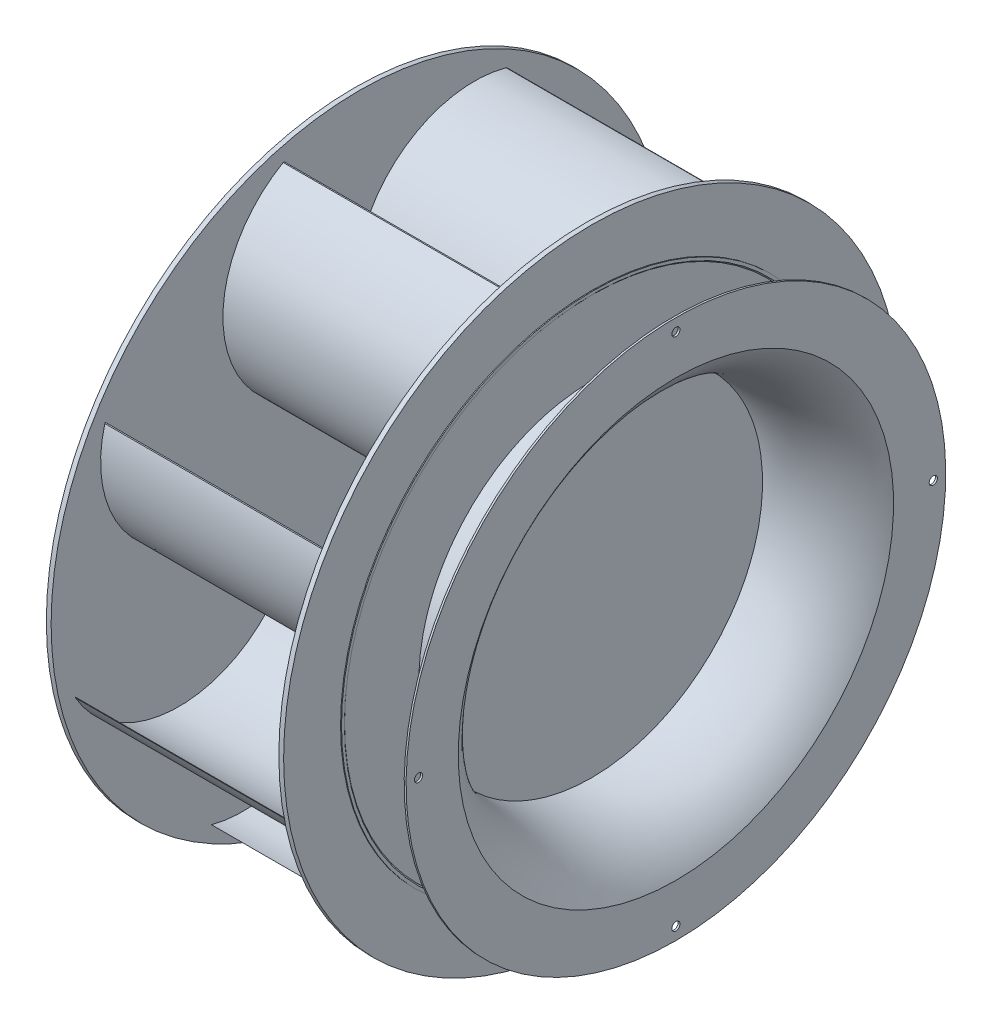
SolidWorks part; units mm, degrees
ref_plane "Front Plane" through (0, 0, 0) normal (0, 0, 1) x (1, 0, 0)
ref_plane "Top Plane" through (0, 0, 0) normal (0, 1, 0) x (1, 0, 0)
ref_plane "Right Plane" through (0, 0, 0) normal (1, 0, 0) x (0, 0, -1)
sketch "Sketch1" plane through (0, 0, 0) normal (0, 0, 1) x (1, 0, 0)
  line L0 (0, 0) -> (831.9083, 0) construction
  line L1 (0, 0) -> (0, 109)
  line L2 (5, 114) -> (70, 114)
  line L3 (70, 114) -> (70, 138)
  line L4 (70, 138) -> (90, 138)
  line L5 (90, 138) -> (90, 98)
  line L6 (90, 98) -> (95, 98)
  line L7 (95, 98) -> (95, 133)
  line L8 (95, 133) -> (105, 133)
  line L9 (105, 133) -> (105, 98)
  line L10 (105, 98) -> (129, 98)
  line L11 (129, 98) -> (129, 0)
  line L12 (129, 0) -> (0, 0)
  arc A0 (5, 114) -> (0, 109) centre (5, 109) ccw
  point P16 (0, 114)
  dimension "D10" = 5
  dimension "D1" = 114
  dimension "D2" = 24
  dimension "D3" = 70
  dimension "D4" = 40
  dimension "D5" = 35
  dimension "D6" = 5
  dimension "D7" = 20
  dimension "D8" = 10
  dimension "D9" = 59
revolve "Revolve1" add sketch "Sketch1" angle 360 about L0
sketch "Sketch2" plane through (129, 0, 0) normal (1, 0, 0) x (0, 0, -1)
  circle A0 centre (0, 0) radius 322
  dimension "D1" = 644
extrude "Extrude1" add sketch "Sketch2" along normal blind 5
sketch "Sketch9" plane through (129, 0, 0) normal (-1, 0, 0) x (0, 0, 1)
  circle A0 centre (0, 0) radius 317
  circle A1 centre (0, 0) radius 100
  circle A2 centre (0, 0) radius 322 construction
  dimension "D1" = 5
  dimension "D2" = 200
extrude "Extrude7" cut sketch "Sketch9" against normal blind 3
ref_plane "Plane1" through (372, 0, 0) normal (1, 0, 0) x (0, 0, -1)
sketch "Sketch3" plane through (372, 0, 0) normal (1, 0, 0) x (0, 0, -1)
  circle A0 centre (0, 0) radius 322
  dimension "D1" = 644
extrude "Extrude2" add sketch "Sketch3" along normal blind 5 separate body
sketch "Sketch4" plane through (134, 0, 0) normal (1, 0, 0) x (0, 0, -1)
  line L0 (0, 0) -> (0, 307) construction
  line L1 (0, 0) -> (161, 278.8602) construction
  line L2 (0, 112.5) -> (0.866, 112)
  line L3 (153.5, 265.8698) -> (154.366, 265.3698)
  circle A0 centre (0, 0) radius 307 construction
  circle A1 centre (0, 0) radius 322 construction
  circle A2 centre (0, 0) radius 112.5 construction
  arc A3 (0, 112.5) -> (153.5, 265.8698) centre (120.6282, 145.2694) cw
  arc A4 (0.866, 112) -> (154.366, 265.3698) centre (121.4942, 144.7694) cw
  dimension "D1" = 15
  dimension "D2" = 225
  dimension "D6" = 125
  dimension "D7" = 125
  dimension "D3" = 30
  dimension "D4" = 60
  dimension "D5" = 1
extrude "Extrude3" add sketch "Sketch4" along normal up to surface (243 mm away) up to face at (377, 0, -322)
ref_axis "Axis1" through (253.5503, 0, 0) along (-1, 0, 0)
pattern_circular "CirPattern1" count 8 over 360 about axis through (253.5503, 0, 0) along (-1, 0, 0) of "Extrude3"
sketch "Sketch5" plane through (0, 0, 0) normal (0, 0, 1) x (1, 0, 0)
  line L0 (0, 0) -> (527.2916, 0) construction
  line L1 (253.5503, 0) -> (75.411, 0) construction
  line L2 (377, 262.5) -> (378, 262.5)
  line L3 (378, 262.5) -> (378, 259.5)
  line L4 (377, 262.5) -> (377, 259.5)
  line L5 (367, 182.5) -> (367, 181.5)
  line L6 (70, 138) -> (70, -138) construction
  line L7 (377, -322) -> (377, 322) construction
  arc A0 (378, 259.5) -> (367, 182.5) centre (430.1173, 212.769) ccw
  arc A1 (377, 259.5) -> (367, 181.5) centre (429.4436, 213.1354) ccw
  dimension "D7" = 70
  dimension "D8" = 70
  dimension "D1" = 181.5
  dimension "D2" = 1
  dimension "D3" = 1
  dimension "D4" = 3
  dimension "D5" = 262.5
  dimension "D6" = 297
revolve "Revolve2" add sketch "Sketch5" angle 360 about L0
ref_plane "Plane3" through (465, 0, 0) normal (1, 0, 0) x (0, 0, -1)
sketch "Sketch6" plane through (0, 0, 0) normal (0, 0, 1) x (1, 0, 0)
  line L0 (465, 282) -> (463, 282)
  line L1 (465, -251.35) -> (465, 251.35) construction
  line L2 (463, 282) -> (463, 227.5)
  line L3 (0, 0) -> (615.1417, 0) construction
  line L4 (0, 114) -> (0, -114) construction
  line L5 (253.5503, 0) -> (75.411, 0) construction
  line L6 (465, 282) -> (465, 227.5)
  line L7 (361, 181.5) -> (365, 181.5)
  line L8 (361, 181.5) -> (361, 179.5)
  line L9 (361, 179.5) -> (365, 179.5)
  arc A0 (365, 181.5) -> (463, 227.5) centre (378.2724, 280.6153) ccw
  arc A1 (365, 179.5) -> (465, 227.5) centre (378.9922, 278.5163) ccw
  dimension "D7" = 100
  dimension "D8" = 100
  dimension "D1" = 282
  dimension "D2" = 2
  dimension "D3" = 227.5
  dimension "D4" = 104
  dimension "D5" = 181.5
  dimension "D6" = 4
revolve "Revolve3" add sketch "Sketch6" angle 360 about L3
sketch "Sketch7" plane through (465, 0, 0) normal (1, 0, 0) x (0, 0, -1)
  line L0 (0, 0) -> (0, 269) construction
  circle A0 centre (0, 0) radius 269 construction
  circle A1 centre (0, 269) radius 4.25
  dimension "D1" = 538
  dimension "D2" = 8.5
extrude "Extrude5" cut sketch "Sketch7" against normal blind 5
pattern_circular "CirPattern2" count 4 over 360 about axis through (253.5503, 0, 0) along (-1, 0, 0) of "Extrude5"
sketch "Sketch8" plane through (0, 0, 0) normal (1, 0, 0) x (0, 0, -1)
  line L0 (0, 0) -> (0, 126) construction
  circle A0 centre (0, 0) radius 126 construction
  circle A1 centre (0, 126) radius 5
  dimension "D1" = 252
  dimension "D2" = 10
extrude "Extrude6" cut sketch "Sketch8" along normal up to surface (90 mm away) up to face at (90, 0, 138)
pattern_circular "CirPattern3" count 8 over 360 about axis through (253.5503, 0, 0) along (-1, 0, 0) of "Extrude6"
